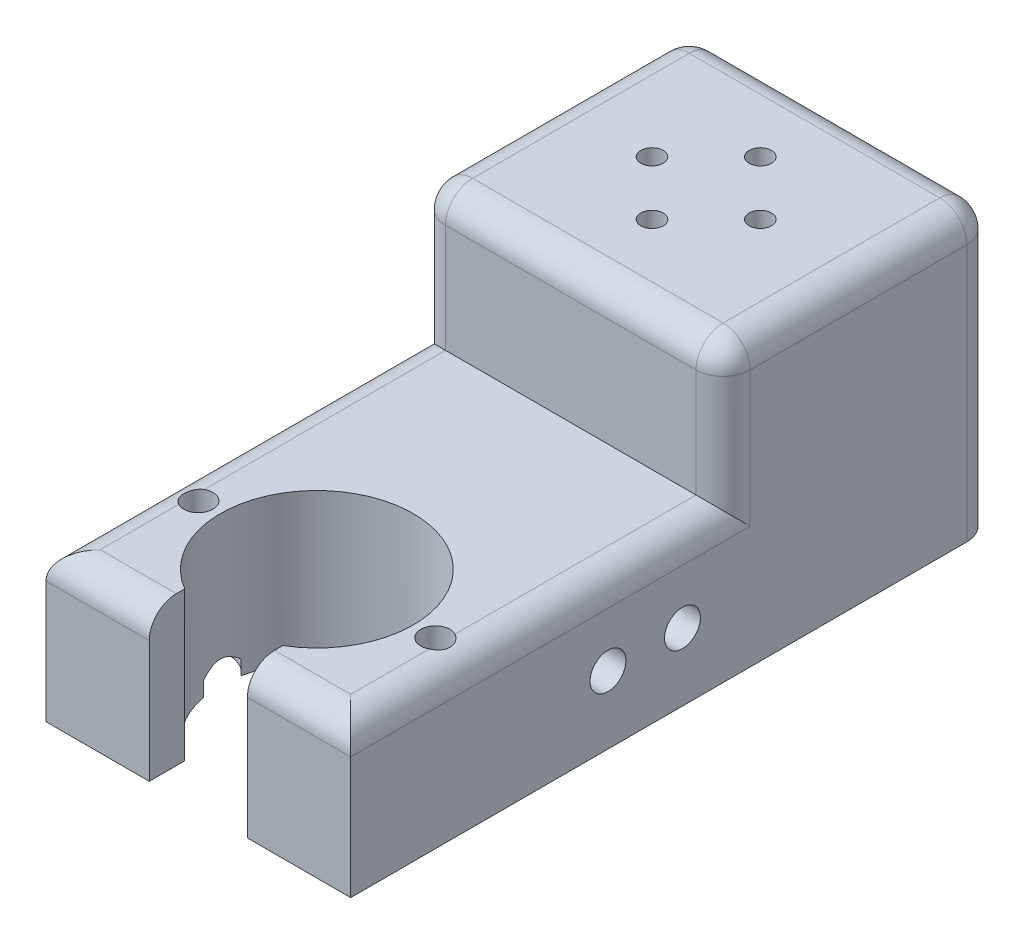
SolidWorks part; units mm, degrees
ref_plane "Front Plane" through (0, 0, 0) normal (0, 0, 1) x (1, 0, 0)
ref_plane "Top Plane" through (0, 0, 0) normal (0, 1, 0) x (1, 0, 0)
ref_plane "Right Plane" through (0, 0, 0) normal (1, 0, 0) x (0, 0, -1)
sketch "Sketch1" plane through (0, 0, 0) normal (0, 1, 0) x (1, 0, 0)
  line L1 (-22.5, -17.5) -> (22.5, -17.5)
  line L2 (-22.5, -17.5) -> (-22.5, 17.5)
  line L3 (-22.5, 17.5) -> (22.5, 17.5)
  line L4 (22.5, -17.5) -> (22.5, 17.5)
  line L5 (-22.5, -17.5) -> (22.5, 17.5) construction
  line L6 (-22.5, 17.5) -> (22.5, -17.5) construction
  point P0 (0, 0)
  dimension "D1" = 45
  dimension "D2" = 35
extrude "Boss-Extrude1" add sketch "Sketch1" along normal blind 22
sketch "Sketch4" plane through (0, 22, 0) normal (0, 1, 0) x (1, 0, 0)
  circle A0 centre (0, 0) radius 14.25
  dimension "D1" = 28.5
extrude "Cut-Extrude3" cut sketch "Sketch4" against normal through all
sketch "Sketch3" plane through (0, 0, 0) normal (0, 1, 0) x (1, 0, 0)
  line L0 (-22.5, -17.5) -> (22.5, -17.5) construction
  line L1 (-7.25, -17.5) -> (7.25, -17.5)
  line L2 (-7.25, -17.5) -> (-7.25, -12.2678)
  line L3 (-7.25, -12.2678) -> (7.25, -12.2678)
  line L4 (7.25, -17.5) -> (7.25, -12.2678)
  circle A0 centre (0, 0) radius 14.25 construction
  point P6 (0, -12.2678)
  dimension "D2" = 14.5
extrude "Cut-Extrude2" cut sketch "Sketch3" along normal through all
sketch "Sketch6" plane through (0, 22, 0) normal (0, 1, 0) x (1, 0, 0)
  line L0 (17.5, 0) -> (-17.5, 0) construction
  circle A0 centre (-17.5, 0) radius 2.15
  circle A1 centre (17.5, 0) radius 2.15
  point P0 (0, 0)
  dimension "D1" = 4.3
  dimension "D2" = 4.3
  dimension "D3" = 35
extrude "Cut-Extrude4" cut sketch "Sketch6" against normal through all
sketch "Sketch7" plane through (0, 0, 0) normal (0, -1, 0) x (1, 0, 0)
  circle A0 centre (-17.5, 0) radius 4.5
  circle A1 centre (17.5, 0) radius 4.5
  dimension "D1" = 9
  dimension "D2" = 9
extrude "Cut-Extrude5" cut sketch "Sketch7" against normal blind 4
chamfer "Chamfer1" distance 1.85 angle 45 2 edges at (-22, 4, 0) (22, 4, 0)
sketch "Sketch8" plane through (0, 0, -17.5) normal (0, 0, -1) x (-1, 0, 0)
  line L4 (-22.5, 0) -> (22.5, 0)
  line L5 (22.5, 0) -> (22.5, 22)
  line L6 (22.5, 22) -> (-22.5, 22)
  line L7 (-22.5, 22) -> (-22.5, 0)
  line L8 (-22.5, 0) -> (22.5, 0)
  line L9 (22.5, 0) -> (22.5, 22)
  line L10 (22.5, 22) -> (-22.5, 22)
  line L11 (-22.5, 22) -> (-22.5, 0)
  dimension "D1" = 0
extrude "Boss-Extrude2" add sketch "Sketch8" along normal blind 60
sketch "Sketch9" plane through (0, 22, 0) normal (0, 1, 0) x (1, 0, 0)
  line L1 (-22.5, 77.5) -> (22.5, 77.5)
  line L2 (-22.5, 77.5) -> (-22.5, 37.5)
  line L3 (-22.5, 37.5) -> (22.5, 37.5)
  line L4 (22.5, 77.5) -> (22.5, 37.5)
  line L5 (22.5, -17.5) -> (22.5, 77.5) construction
  dimension "D1" = 40
  dimension "D2" = 45
extrude "Boss-Extrude3" add sketch "Sketch9" along normal blind 20
ref_plane "Plane1" through (0, 0, -57.5) normal (0, 0, 1) x (1, 0, 0)
sketch "Sketch10" plane through (0, 0, 0) normal (0, -1, 0) x (1, 0, 0)
  line L0 (22.5, -37.5) -> (-22.5, -37.5) construction
  line L1 (0, -37.5) -> (0, -77.5) construction
  line L2 (22.5, -77.5) -> (-22.5, -77.5) construction
  line L3 (22.5, -37.5) -> (22.5, -77.5) construction
  line L4 (22.5, -57.5) -> (-22.5, -57.5) construction
  line L5 (23.1, -57.5) -> (-23.1, -57.5) construction
  line L7 (-14, -71.5) -> (14, -71.5)
  line L8 (-14, -71.5) -> (-14, -43.5)
  line L9 (-14, -43.5) -> (14, -43.5)
  line L10 (14, -71.5) -> (14, -43.5)
  line L11 (-14, -71.5) -> (14, -43.5) construction
  line L12 (-14, -43.5) -> (14, -71.5) construction
  point P14 (0, -57.5)
  dimension "D1" = 28
extrude "Cut-Extrude6" cut sketch "Sketch10" against normal blind 30
hole_wizard "Ø3.0mm Dowel Hole1" positions "Sketch13" profile "Sketch14" hole size "Ø3.0" standard "ANSI Metric"
sketch "Sketch13" plane through (0, 42, 0) normal (0, 1, 0) x (1, 0, 0)
  point P0 (-8, 57.5)
  point P3 (0, 49.5)
  point P6 (0, 65.5)
  point P9 (8, 57.5)
sketch "Sketch14" plane through (-8, 42, -57.5) normal (1, 0, 0) x (0, 0, 1)
  line L0 (0, 0) -> (0, 15.9914)
  line L1 (0, 15.9914) -> (1.65, 15)
  line L2 (1.65, 15) -> (1.65, 0)
  line L5 (1.65, 0) -> (0, 0)
  line L10 (0, 15.9914) -> (-1.65, 15) construction
  line L11 (0, -6.35) -> (0, 107.95) construction
  dimension "Hole Dia." = 3.3
  dimension "Hole Depth" = 15
  dimension "Drill Angle" = 118
hole_wizard "Ø5.0mm Dowel Hole1" positions "Sketch15" profile "Sketch17" hole size "Ø5.0" standard "ANSI Metric"
sketch "Sketch15" plane through (-22.5, 0, 0) normal (-1, 0, 0) x (0, 0, 1)
  point P0 (-31.5, 10)
  point P3 (-20.5, 10)
sketch "Sketch17" plane through (-22.5, 10, -31.5) normal (0, 1, 0) x (0, 0, 1)
  line L0 (0, 0) -> (0, 16.5923)
  line L1 (0, 16.5923) -> (2.65, 15)
  line L2 (2.65, 15) -> (2.65, 0)
  line L5 (2.65, 0) -> (0, 0)
  line L10 (0, 16.5923) -> (-2.65, 15) construction
  line L11 (0, -6.35) -> (0, 107.95) construction
  dimension "Hole Dia." = 5.3
  dimension "Hole Depth" = 15
  dimension "Drill Angle" = 118
sketch "Sketch18" plane through (0, 0, 0) normal (0, -1, 0) x (1, 0, 0)
  line L1 (-17.5, -39.5) -> (-10.5, -39.5)
  line L2 (-17.5, -39.5) -> (-17.5, -14.5)
  line L3 (-17.5, -14.5) -> (-10.5, -14.5)
  line L4 (-10.5, -39.5) -> (-10.5, -14.5)
  line L9 (22.5, -77.5) -> (-22.5, -77.5) construction
  line L10 (-22.5, -77.5) -> (-22.5, 17.5) construction
  dimension "D1" = 7
  dimension "D2" = 25
  dimension "D3" = 38
  dimension "D4" = 5
extrude "Cut-Extrude7" cut sketch "Sketch18" against normal blind 16
mirror "Mirror1" about plane through (0, 0, 0) normal (1, 0, 0) of "Cut-Extrude7"
hole_wizard "Ø5.0mm Dowel Hole2" positions "Sketch20" profile "Sketch21" hole size "Ø5.0" standard "ANSI Metric"
sketch "Sketch20" plane through (22.5, 0, 0) normal (1, 0, 0) x (0, 0, -1)
  point P0 (20.5, 10)
  point P3 (31.5, 10)
sketch "Sketch21" plane through (22.5, 10, -20.5) normal (0, 1, 0) x (0, 0, -1)
  line L0 (0, 0) -> (0, 16.5923)
  line L1 (0, 16.5923) -> (2.65, 15)
  line L2 (2.65, 15) -> (2.65, 0)
  line L5 (2.65, 0) -> (0, 0)
  line L10 (0, 16.5923) -> (-2.65, 15) construction
  line L11 (0, -6.35) -> (0, 107.95) construction
  dimension "Hole Dia." = 5.3
  dimension "Hole Depth" = 15
  dimension "Drill Angle" = 118
chamfer "Chamfer2" distance 3 angle 45 4 edges at (0, 30, -43.5) (14, 30, -57.5) (0, 30, -71.5) (-14, 30, -57.5)
fillet "Fillet2" radius 4 12 edges at (22.5, 22, -10) (22.5, 32, -37.5) (-22.5, 32, -37.5) (-22.5, 22, -10) (0, 42, -37.5) (22.5, 42, -57.5) (0, 42, -77.5) (-22.5, 42, -57.5) (-22.5, 21, -77.5) (22.5, 21, -77.5) (14.875, 22, 17.5) (-14.875, 22, 17.5)
